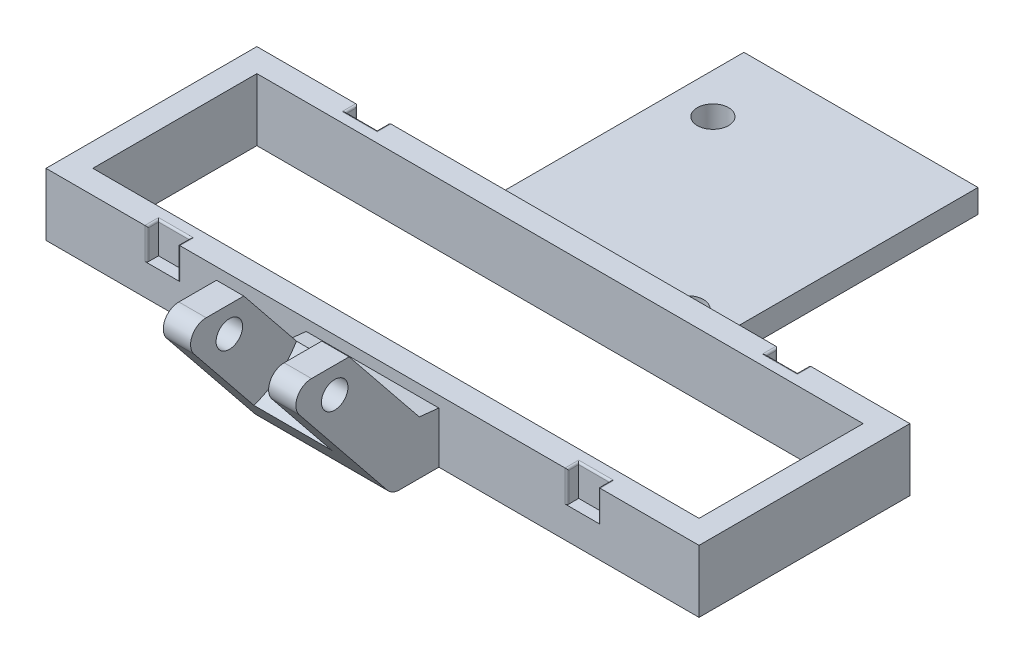
SolidWorks part; units mm, degrees
ref_plane "Front Plane" through (0, 0, 0) normal (0, 0, 1) x (1, 0, 0)
ref_plane "Top Plane" through (0, 0, 0) normal (0, 1, 0) x (1, 0, 0)
ref_plane "Right Plane" through (0, 0, 0) normal (1, 0, 0) x (0, 0, -1)
sketch "Sketch5" plane through (0, 0, 0) normal (0, 1, 0) x (1, 0, 0)
  line L0 (30, -35.5764) -> (56.85, -35.5764)
  line L1 (0, 0) -> (30, 0)
  line L2 (0, 0) -> (0, -35.5764)
  line L4 (30, 0) -> (30, -35.5764)
  line L5 (-26.85, -35.5764) -> (0, -35.5764)
  line L6 (-26.85, -35.5764) -> (-26.85, -62.6044)
  line L7 (-26.85, -62.6044) -> (56.85, -62.6044)
  line L8 (56.85, -35.5764) -> (56.85, -62.6044)
  line L9 (15, 0) -> (15, -62.6044) construction
  line L10 (-23.85, -38.5764) -> (53.85, -38.5764)
  line L11 (-23.85, -38.5764) -> (-23.85, -59.6044)
  line L12 (-23.85, -59.6044) -> (53.85, -59.6044)
  line L13 (53.85, -38.5764) -> (53.85, -59.6044)
  line L14 (-26.85, -49.0904) -> (56.85, -49.0904) construction
  line L16 (-23.75, -38.6764) -> (53.75, -38.6764) construction
  line L17 (-23.75, -38.6764) -> (-23.75, -59.5044) construction
  line L18 (-23.75, -59.5044) -> (53.75, -59.5044) construction
  line L19 (53.75, -38.6764) -> (53.75, -59.5044) construction
  line L20 (-23.75, -38.6764) -> (53.75, -59.5044) construction
  line L21 (-23.75, -59.5044) -> (53.75, -38.6764) construction
  point P18 (15, -38.5764)
  point P19 (53.85, -49.0904)
  point P21 (15, -49.0904)
  dimension "D1" = 77.5
  dimension "D2" = 30
  dimension "D3" = 20.828
  dimension "D4" = 0.1
  dimension "D5" = 0.1
  dimension "D6" = 3
  dimension "D7" = 3
extrude "Boss-Extrude3" add sketch "Sketch5" along normal blind 8
sketch "Sketch6" plane through (0, 8, 0) normal (0, 1, 0) x (1, 0, 0)
  line L1 (0, 0) -> (30, 0)
  line L2 (0, 0) -> (0, -35.5764)
  line L3 (0, -35.5764) -> (30, -35.5764)
  line L4 (30, 0) -> (30, -35.5764)
extrude "Cut-Extrude4" cut sketch "Sketch6" against normal offset from surface (5 mm away) 3 up to face at (15, 0, 33.4393)
sketch "Sketch7" plane through (0, 0, 0) normal (0, -1, 0) x (1, 0, 0)
  line L0 (-26.85, 62.6044) -> (56.85, 62.6044) construction
  line L3 (6.5, 59.6044) -> (23.5, 59.6044)
  line L5 (6.5, 65.6044) -> (23.5, 59.6044) construction
  line L6 (6.5, 59.6044) -> (23.5, 65.6044) construction
  line L7 (-23.85, 59.6044) -> (53.85, 59.6044) construction
  line L8 (6.5, 68.6044) -> (6.5, 59.6044)
  line L9 (6.5, 68.6044) -> (23.5, 68.6044)
  line L13 (6.5, 68.6044) -> (23.5, 62.6044) construction
  line L14 (6.5, 62.6044) -> (23.5, 68.6044) construction
  line L15 (23.5, 68.6044) -> (23.5, 59.6044)
  point P0 (15, 62.6044)
  point P9 (15, 65.6044)
  dimension "D1" = 17
ref_plane "Plane1" through (15, 0, 0) normal (1, 0, 0) x (0, 0, -1)
sketch "Sketch8" plane through (15, 0, 0) normal (1, 0, 0) x (0, 0, -1)
  line L0 (-62.6044, 0) -> (-62.6044, 18) construction
  line L1 (-62.6044, 18) -> (-80.6044, 18) construction
  dimension "D1" = 18
  dimension "D2" = 18
ref_plane "Plane2" through (0, 18, 0) normal (0, -1, 0) x (-1, 0, 0)
sketch "Sketch9" plane through (0, 18, 0) normal (0, -1, 0) x (-1, 0, 0)
  line L0 (-15, -62.6044) -> (-15, -80.6044) construction
  line L6 (-23.5, -83.1044) -> (-6.5, -83.1044)
  line L7 (-23.5, -83.1044) -> (-23.5, -74.1044)
  line L8 (-23.5, -74.1044) -> (-6.5, -74.1044)
  line L9 (-6.5, -83.1044) -> (-6.5, -74.1044)
  line L10 (-23.5, -83.1044) -> (-6.5, -74.1044) construction
  line L11 (-23.5, -74.1044) -> (-6.5, -83.1044) construction
  point P0 (-15, -78.6044)
  point P1 (-15, -78.6044)
  dimension "D1" = 17
  dimension "D2" = 9
loft "Loft1" add profiles "Sketch7", "Sketch9"
sketch "Sketch10" plane through (23.5, 0, 0) normal (1, 0, 0) x (0, 0, -1)
  line L0 (-67.5788, 9.8993) -> (-73.0369, 5.5024) construction
  line L1 (-73.0369, 5.5024) -> (-74.0977, 6.8192) construction
  line L3 (-70.3079, 7.7008) -> (-75.9538, 14.7096) construction
  line L4 (-62.6044, 3.7241) -> (-74.1044, 18) construction
  line L5 (-68.6044, 0) -> (-83.1044, 18) construction
  circle A1 centre (-75.9538, 14.7096) radius 1.7
  dimension "D1" = 3.4
  dimension "D2" = 9
  dimension "D3" = 90
  dimension "D4" = 90
extrude "Cut-Extrude5" cut sketch "Sketch10" against normal up to surface (17 mm away) up to face at (6.5, 4.3448, 69.1044)
fillet "Fillet4" radius 2 1 edges
fillet "Fillet5" radius 2 1 edges
chamfer "Chamfer1" distance 4 angle 45 1 edges at (15, 3.7241, 62.6044) first distance on face at (12.875, 7.2931, 65.4794)
ref_plane "Plane3" through (15, 0, 0) normal (1, 0, 0) x (0, 0, -1)
sketch "Sketch11" plane through (15, 0, 0) normal (1, 0, 0) x (0, 0, -1)
  circle A0 centre (-75.9538, 14.7096) radius 10
  dimension "D1" = 20
extrude "Cut-Extrude6" cut sketch "Sketch11" against normal mid plane 10
sketch "Sketch12" plane through (0, 3, 0) normal (0, 1, 0) x (1, 0, 0)
  line L0 (15, -35.5764) -> (15, -32.0264) construction
  line L1 (30, -35.5764) -> (0, -35.5764) construction
  line L2 (15, -20.5236) -> (15, 20.5236) construction
  line L4 (15, -32.0264) -> (15, -9.1264) construction
  line L6 (15, -32.0264) -> (24.85, -32.0264) construction
  line L7 (15, -9.1264) -> (5.15, -9.1264) construction
  circle A2 centre (24.85, -32.0264) radius 2
  circle A3 centre (5.15, -9.1264) radius 2
  dimension "D3" = 9.85
  dimension "D6" = 9.85
  dimension "D2" = 4
  dimension "D5" = 4
  dimension "D1" = 3.55
  dimension "D4" = 22.9
extrude "Cut-Extrude7" cut sketch "Sketch12" against normal up to surface (3 mm away) up to face at (5.2875, 0, 49.0904)
sketch "Sketch13" plane through (0, 8, 0) normal (0, 1, 0) x (1, 0, 0)
  line L0 (0, -35.5764) -> (-23.85, -35.5764) construction
  line L1 (56.85, -35.5764) -> (-26.85, -35.5764) construction
  line L2 (30, -35.5764) -> (53.85, -35.5764) construction
  line L3 (-11.925, -35.5764) -> (-9.925, -35.5764) construction
  line L4 (-23.85, -49.0904) -> (53.85, -49.0904) construction
  line L5 (-9.925, -35.5764) -> (-13.925, -35.5764)
  line L6 (-9.925, -35.5764) -> (-9.925, -37.0764)
  line L7 (-9.925, -37.0764) -> (-13.925, -37.0764)
  line L8 (-13.925, -35.5764) -> (-13.925, -37.0764)
  line L9 (-23.85, -38.5764) -> (-23.85, -59.6044) construction
  line L10 (53.85, -59.6044) -> (53.85, -38.5764) construction
  line L11 (15, -38.5764) -> (15, -59.6044) construction
  line L12 (53.85, -38.5764) -> (-23.85, -38.5764) construction
  line L13 (-23.85, -59.6044) -> (53.85, -59.6044) construction
  line L14 (-11.925, -62.6044) -> (-9.925, -62.6044) construction
  line L15 (-13.925, -62.6044) -> (-13.925, -61.1044)
  line L16 (-9.925, -61.1044) -> (-13.925, -61.1044)
  line L17 (-9.925, -62.6044) -> (-9.925, -61.1044)
  line L18 (-9.925, -62.6044) -> (-13.925, -62.6044)
  line L19 (41.925, -35.5764) -> (39.925, -35.5764) construction
  line L20 (39.925, -62.6044) -> (43.925, -62.6044)
  line L21 (39.925, -62.6044) -> (39.925, -61.1044)
  line L22 (39.925, -61.1044) -> (43.925, -61.1044)
  line L23 (43.925, -62.6044) -> (43.925, -61.1044)
  line L24 (43.925, -35.5764) -> (43.925, -37.0764)
  line L25 (39.925, -37.0764) -> (43.925, -37.0764)
  line L26 (39.925, -35.5764) -> (39.925, -37.0764)
  line L27 (39.925, -35.5764) -> (43.925, -35.5764)
  dimension "D1" = 2
  dimension "D2" = 4
  dimension "D3" = 1.5
extrude "Cut-Extrude8" cut sketch "Sketch13" against normal blind 4
fillet "Fillet6" radius 0.25 20 edges at (41.925, 8, 37.0764) (41.925, 8, 61.1044) (-11.925, 8, 37.0764) (-11.925, 8, 61.1044) (-9.925, 8, 61.8544) (-9.925, 6, 62.6044) (-13.925, 8, 61.8544) (-13.925, 6, 62.6044) (39.925, 8, 61.8544) (43.925, 8, 61.8544) (43.925, 6, 62.6044) (39.925, 6, 62.6044) (43.925, 8, 36.3264) (43.925, 6, 35.5764) (39.925, 8, 36.3264) (39.925, 6, 35.5764) (-9.925, 8, 36.3264) (-9.925, 6, 35.5764) (-13.925, 8, 36.3264) (-13.925, 6, 35.5764)
equation "\"D1@Sketch5\"=77.5"
equation "\"D3@Sketch5\"=0.82in"
